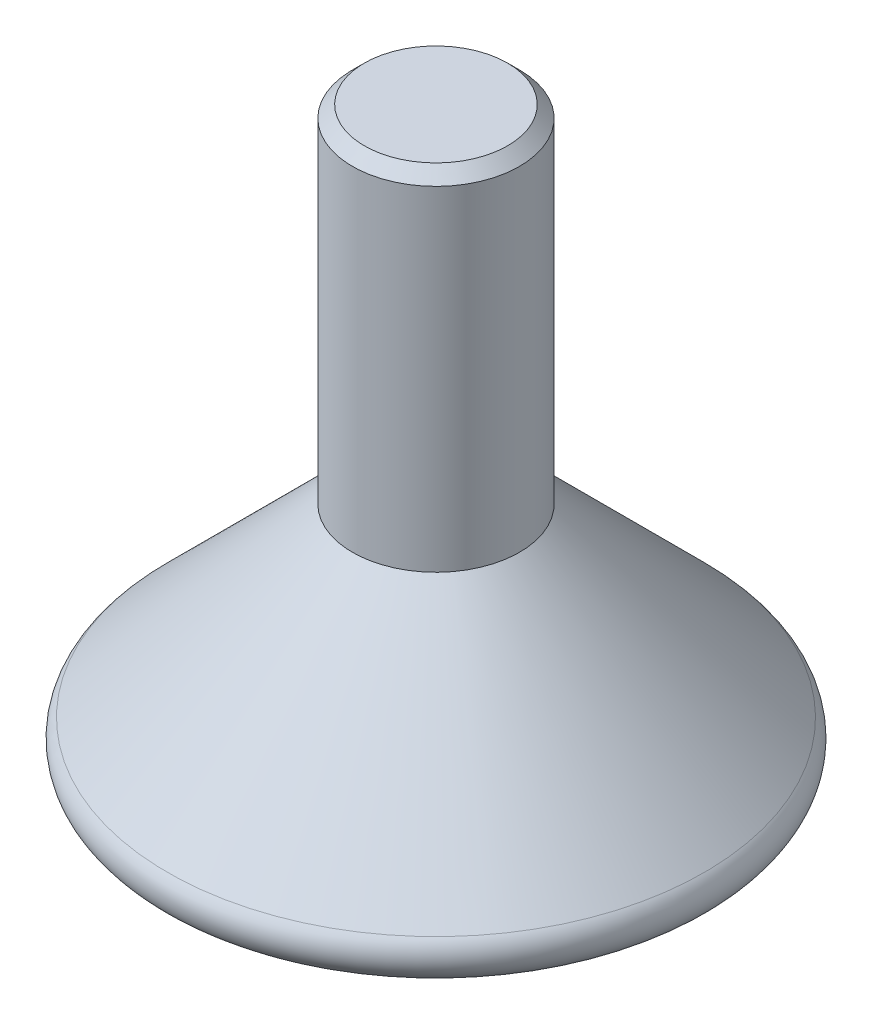
SolidWorks part; units mm, degrees
ref_plane "Alzado" through (0, 0, 0) normal (0, 0, 1) x (1, 0, 0)
ref_plane "Planta" through (0, 0, 0) normal (0, 1, 0) x (1, 0, 0)
ref_plane "Vista lateral" through (0, 0, 0) normal (1, 0, 0) x (0, 0, -1)
sketch "Croquis1" plane through (0, 0, 0) normal (0, 0, 1) x (1, 0, 0)
  line L0 (0, 0) -> (0, 85.9498) construction
  line L1 (-5, 33.6213) -> (-5, 13.6213)
  line L2 (-5, 13.6213) -> (-16.0607, 2.5607)
  line L3 (-15, 0) -> (0, 0)
  line L4 (-15, 0) -> (-15, 5.5806) construction
  line L5 (-16.0607, 2.5607) -> (-13.0109, -0.4891) construction
  line L6 (-5, 33.6213) -> (-4.2883, 34.333)
  line L7 (-4.2883, 34.333) -> (0, 34.333)
  line L8 (-5, 33.6213) -> (1.4006, 33.6213) construction
  line L9 (0, 0) -> (0, 34.333)
  arc A0 (-16.0607, 2.5607) -> (-15, 0) centre (-15, 1.5) ccw
  point P10 (-15, 1.5)
  dimension "D2" = 1.5
  dimension "D1" = 45
  dimension "D3" = 15
  dimension "D4" = 5
  dimension "D6" = 20
  dimension "D7" = 45
  dimension "D8" = 4.2883
revolve "Revolución2" add sketch "Croquis1" angle 360 about L0 region at (-4.842, 12.8447, 0)
